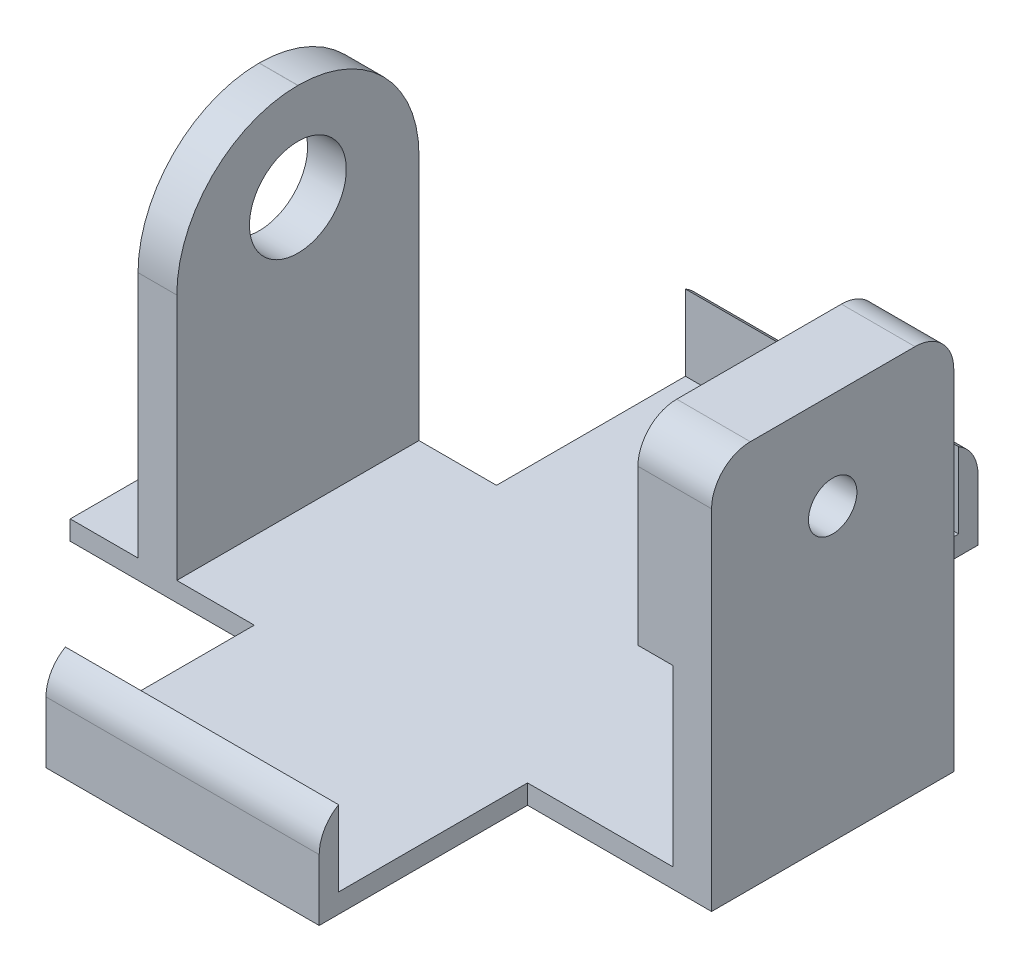
SolidWorks part; units mm, degrees
ref_plane "Front Plane" through (0, 0, 0) normal (0, 0, 1) x (1, 0, 0)
ref_plane "Top Plane" through (0, 0, 0) normal (0, 1, 0) x (1, 0, 0)
ref_plane "Right Plane" through (0, 0, 0) normal (1, 0, 0) x (0, 0, -1)
sketch "Sketch1" plane through (0, 0, 0) normal (0, 1, 0) x (1, 0, 0)
  line L0 (-14.1, 12.5) -> (-14.1, 34)
  line L1 (-14.1, -34) -> (14.1, -34)
  line L2 (-14.1, -34) -> (-14.1, -12.5)
  line L3 (-14.1, 34) -> (14.1, 34)
  line L4 (14.1, -34) -> (14.1, -12.5)
  line L7 (-33.1, 12.5) -> (-14.1, 12.5)
  line L8 (-33.1, 12.5) -> (-33.1, -12.5)
  line L9 (-33.1, -12.5) -> (-14.1, -12.5)
  line L10 (33.1, 12.5) -> (33.1, -12.5)
  line L13 (14.1, 12.5) -> (33.1, 12.5)
  line L15 (14.1, 12.5) -> (14.1, 34)
  line L18 (14.1, -12.5) -> (33.1, -12.5)
  point P0 (0, 0)
  point P6 (0, 0)
  dimension "D1" = 28.2
  dimension "D2" = 25
  dimension "D3" = 19
  dimension "D4" = 68
  dimension "D5" = 66.2
  dimension "D6" = 21.5
extrude "Boss-Extrude1" add sketch "Sketch1" along normal blind 2
sketch "Sketch2" plane through (0, 0, 34) normal (0, 0, 1) x (1, 0, 0)
  line L0 (36.41, 0) -> (-36.41, 0) construction
  line L1 (-14.1, 9.8) -> (14.1, 9.8)
  line L2 (-14.1, 9.8) -> (-14.1, 0)
  line L3 (-14.1, 0) -> (14.1, 0)
  line L4 (14.1, 9.8) -> (14.1, 0)
  line L5 (14.1, 2) -> (14.1, 0) construction
  line L8 (-14.1, 2) -> (-14.1, 0) construction
  dimension "D1" = 9.8
extrude "Boss-Extrude2" add sketch "Sketch2" against normal blind 2
fillet "Fillet1" radius 4 1 edges at (0, 9.8, 34)
mirror "Mirror2" about plane through (0, 0, 0) normal (0, 0, 1) of "Boss-Extrude1", "Fillet1", "Boss-Extrude2"
sketch "Sketch3" plane through (33.1, 0, 0) normal (1, 0, 0) x (0, 0, -1)
  line L0 (-12.5, 2) -> (-12.5, 0) construction
  line L1 (12.5, 0) -> (-12.5, 0)
  line L2 (12.5, 0) -> (12.5, 40)
  line L3 (12.5, 40) -> (-12.5, 40)
  line L4 (-12.5, 0) -> (-12.5, 40)
  circle A0 centre (0, 30) radius 2.5
  point P7 (0, 40)
  dimension "D2" = 5
  dimension "D1" = 40
  dimension "D3" = 10
extrude "Boss-Extrude3" add sketch "Sketch3" against normal blind 7.6
fillet "Fillet2" radius 4 2 edges at (29.3, 40, -12.5) (29.3, 40, 12.5)
ref_plane "Plane1" through (-26.1, 0, 0) normal (-1, 0, 0) x (0, 0, 1)
sketch "Sketch4" plane through (0, 0, 12.5) normal (0, 0, 1) x (1, 0, 0)
  line L0 (33.1, 36) -> (33.1, 0) construction
  line L1 (25.5, 2) -> (29.1, 2)
  line L2 (25.5, 2) -> (25.5, 20)
  line L3 (25.5, 20) -> (29.1, 20)
  line L4 (29.1, 2) -> (29.1, 20)
  line L5 (36.41, 0) -> (-36.41, 0) construction
  dimension "D1" = 4
  dimension "D2" = 20
extrude "Cut-Extrude1" cut sketch "Sketch4" against normal up to next
sketch "Sketch5" plane through (-26.1, 0, 0) normal (-1, 0, 0) x (0, 0, 1)
  line L0 (12.5, 2) -> (12.5, 0) construction
  line L1 (12.5, 0) -> (-12.5, 0)
  line L2 (12.5, 0) -> (12.5, 27.51)
  line L3 (0.01, 40) -> (-0.01, 40)
  line L4 (-12.5, 0) -> (-12.5, 27.51)
  line L5 (12.5, 0) -> (34, 0) construction
  line L6 (-12.5, 20) -> (-12.5, 2) construction
  line L7 (36.41, 0) -> (-36.41, 0) construction
  circle A0 centre (0, 30) radius 5
  arc A1 (12.5, 27.51) -> (0.01, 40) centre (0.01, 27.51) ccw
  arc A2 (-0.01, 40) -> (-12.5, 27.51) centre (-0.01, 27.51) ccw
  point P19 (-12.5, 40)
  dimension "D2" = 10
  dimension "D3" = 12.49
  dimension "D1" = 40
extrude "Boss-Extrude4" add sketch "Sketch5" against normal blind 4
